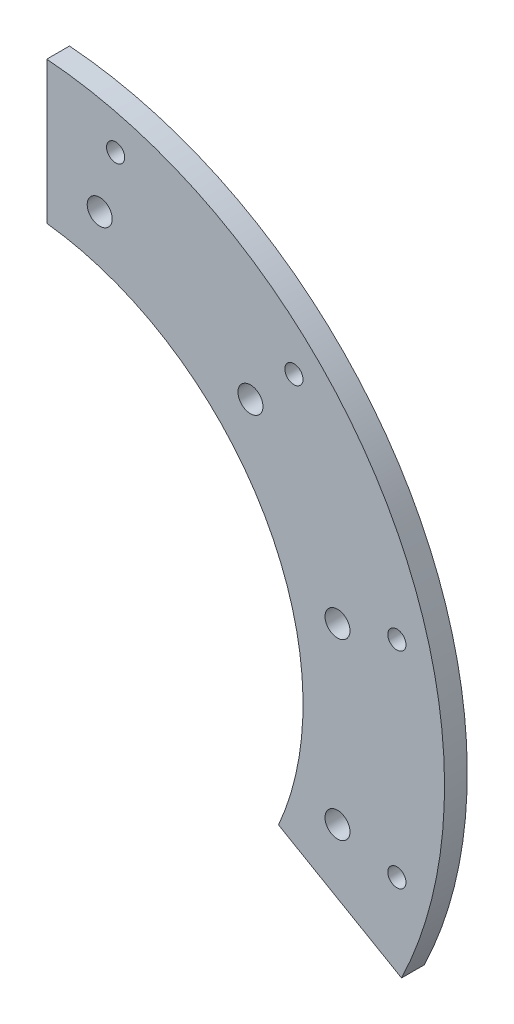
SolidWorks part; units mm, degrees
material "Teck"
ref_plane "Plan de face" through (0, 0, 0) normal (0, 0, 1) x (1, 0, 0)
ref_plane "Plan de dessus" through (0, 0, 0) normal (0, 1, 0) x (1, 0, 0)
ref_plane "Plan de droite" through (0, 0, 0) normal (1, 0, 0) x (0, 0, -1)
sketch "Esquisse1" plane through (0, 0, 0) normal (0, 0, 1) x (1, 0, 0)
  line L0 (6, 75.7628) -> (6, 50.7465)
  line L1 (68.4339, -33.0575) -> (46.7826, -20.5572)
  line L2 (0, 73.61) -> (0, 0) construction
  line L3 (0, 0) -> (63.7481, -36.805) construction
  arc A0 (6, 50.7465) -> (46.7826, -20.5572) centre (0, 0) cw
  arc A2 (6, 75.7628) -> (68.4339, -33.0575) centre (0, 0) cw
  circle A3 centre (0, 0) radius 73.61 construction
  dimension "D4" = 76
  dimension "D5" = 51.1
  dimension "D1" = 120
  dimension "D2" = 6
  dimension "D3" = 6
extrude "Boss.-Extru.1" add sketch "Esquisse1" along normal blind 4 contours L0 A0 L1 A2
sketch "Sketch2" plane through (0, 0, 4) normal (0, 0, 1) x (1, 0, 0)
  line L0 (0, 0) -> (0, 96.9743) construction
  line L1 (0, 0) -> (18.1173, 67.6148) construction
  line L2 (18.1173, 67.6148) -> (29.3318, 109.4676) construction
  circle A0 centre (18.1173, 67.6148) radius 1.6
  circle A1 centre (15.3169, 57.1635) radius 2.2
  dimension "D2" = 3.2
  dimension "D4" = 4.4
  dimension "D1" = 70
  dimension "D3" = 59.18
  dimension "D5" = 15
extrude "Cut-Extrude1" cut sketch "Sketch2" against normal through all
ref_axis "Axis1" through (0, 0, -0.2) along (0, 0, 1)
pattern_circular "CirPattern1" count 12 over 360 about axis through (0, 0, -0.2) along (0, 0, 1) of "Cut-Extrude1" reverse direction yes
